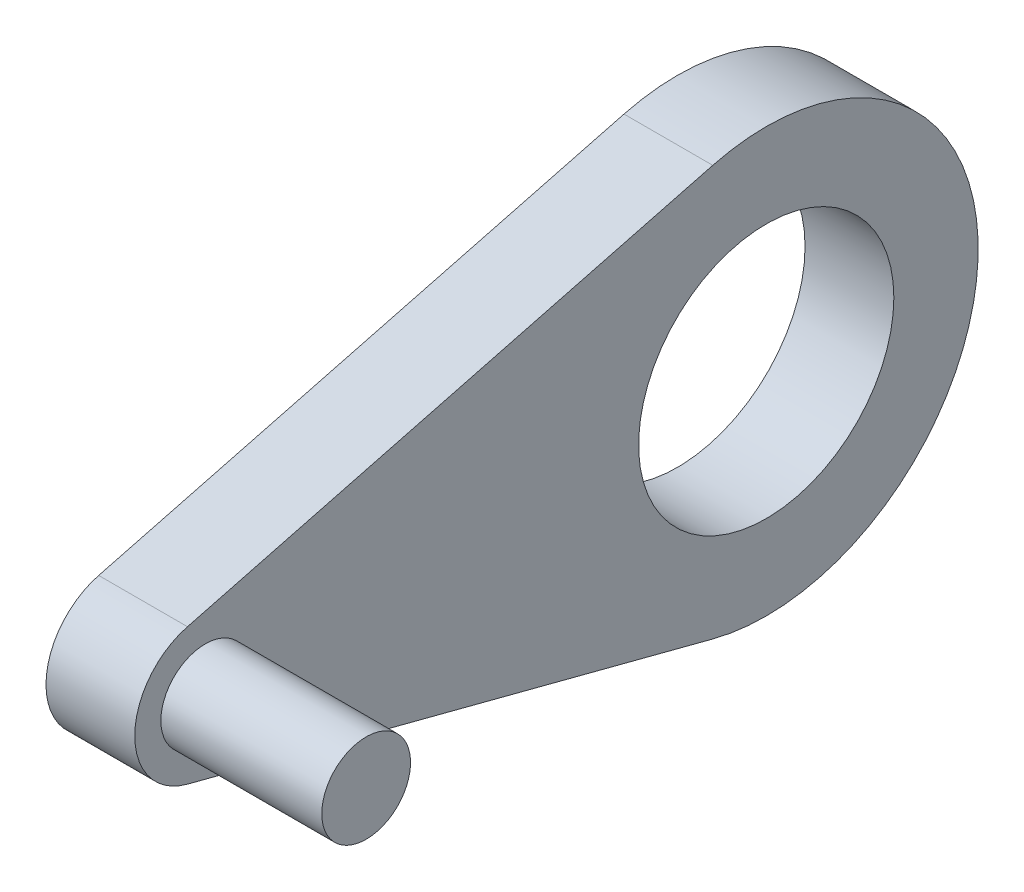
SolidWorks part; units mm, degrees
ref_plane "Front Plane" through (0, 0, 0) normal (0, 0, 1) x (1, 0, 0)
ref_plane "Top Plane" through (0, 0, 0) normal (0, 1, 0) x (1, 0, 0)
ref_plane "Right Plane" through (0, 0, 0) normal (1, 0, 0) x (0, 0, -1)
sketch "Sketch1" plane through (0, 0, 0) normal (1, 0, 0) x (0, 0, -1)
  line L0 (-3.2033, 12.2894) -> (91.465, 36.9649)
  line L1 (91.465, -36.9649) -> (-3.2033, -12.2894)
  arc A0 (-3.2033, 12.2894) -> (-3.2033, -12.2894) centre (0, 0) ccw
  arc A1 (91.465, -36.9649) -> (91.465, 36.9649) centre (101.1, 0) ccw
  dimension "D1" = 101.1
  dimension "D2" = 76.4
  dimension "D3" = 25.4
extrude "Boss-Extrude1" add sketch "Sketch1" against normal blind 16
sketch "Sketch2" plane through (0, 0, 0) normal (1, 0, 0) x (0, 0, -1)
  circle A0 centre (0, 0) radius 8
extrude "Boss-Extrude2" add sketch "Sketch2" along normal blind 29
sketch "Sketch3" plane through (0, 0, 0) normal (1, 0, 0) x (0, 0, -1)
  circle A0 centre (101.1, 0) radius 23
extrude "Cut-Extrude1" cut sketch "Sketch3" along direction (1, 0, 0) on the side against the normal blind 16
ref_point "Point1"
ref_point "Point2"
ref_axis "Axis1" through (-16, 0, -101.1) along (1, 0, 0)
